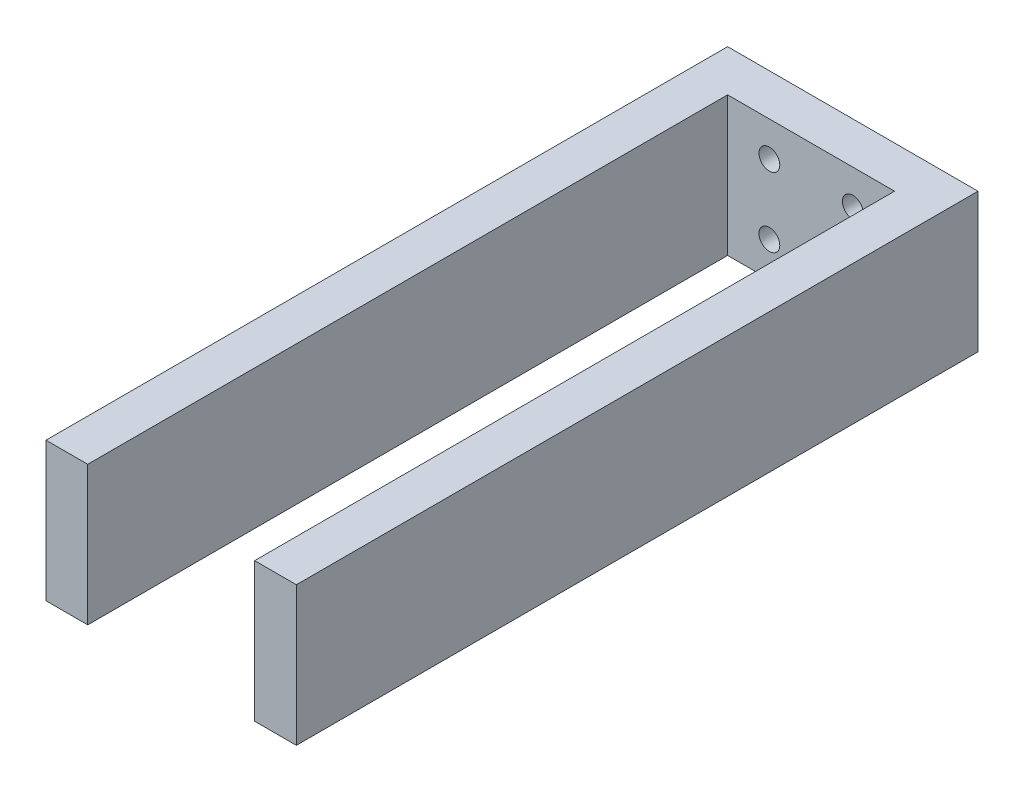
SolidWorks part; units mm, degrees
ref_plane "Спереди" through (0, 0, 0) normal (0, 0, 1) x (1, 0, 0)
ref_plane "Сверху" through (0, 0, 0) normal (0, 1, 0) x (1, 0, 0)
ref_plane "Справа" through (0, 0, 0) normal (1, 0, 0) x (0, 0, -1)
sketch "Эскиз1" plane through (0, 0, 0) normal (0, 0, 1) x (1, 0, 0)
  line L1 (-18, -10) -> (18, -10)
  line L2 (-18, -10) -> (-18, 10)
  line L3 (-18, 10) -> (18, 10)
  line L4 (18, -10) -> (18, 10)
  line L5 (-18, -10) -> (18, 10) construction
  line L6 (-18, 10) -> (18, -10) construction
  line L7 (-18, 10) -> (-12, 10)
  line L8 (-18, 10) -> (-18, -10)
  line L9 (-18, -10) -> (-12, -10)
  line L10 (-12, 10) -> (-12, -10)
  line L11 (18, 10) -> (12, 10)
  line L12 (18, 10) -> (18, -10)
  line L13 (18, -10) -> (12, -10)
  line L14 (12, 10) -> (12, -10)
  circle A0 centre (-6, 5) radius 1.5
  circle A1 centre (6, 5) radius 1.5
  circle A2 centre (-6, -5) radius 1.5
  circle A3 centre (6, -5) radius 1.5
  point P1 (0, 0)
  dimension "D6" = 3
  dimension "D7" = 3
  dimension "D8" = 3
  dimension "D9" = 3
  dimension "D17" = 5
  dimension "D1" = 36
  dimension "D2" = 20
  dimension "D3" = 6
  dimension "D4" = 6
  dimension "D5" = 24
  dimension "D10" = 6
  dimension "D11" = 6
  dimension "D12" = 6
  dimension "D13" = 6
  dimension "D14" = 5
  dimension "D15" = 5
  dimension "D16" = 5
extrude "Бобышка-Вытянуть1" add sketch "Эскиз1" along normal blind 6 contours L10 L3 L2 L1 | L14 L3 L10 L1 | L3 L14 L1 L4 region at (-15, 0, 0) region at (0, 0, 0) region at (15, 0, 0)
extrude "Бобышка-Вытянуть2" add sketch "Эскиз1<3>" along normal blind 98 contours L3 L14 L1 L4 | L10 L3 L2 L1 region at (-15, 0, 0) region at (15, 0, 0)
sketch "Эскиз1<3>" plane through (0, 0, 0) normal (0, 0, 1) x (1, 0, 0) same geometry as "Эскиз1"
